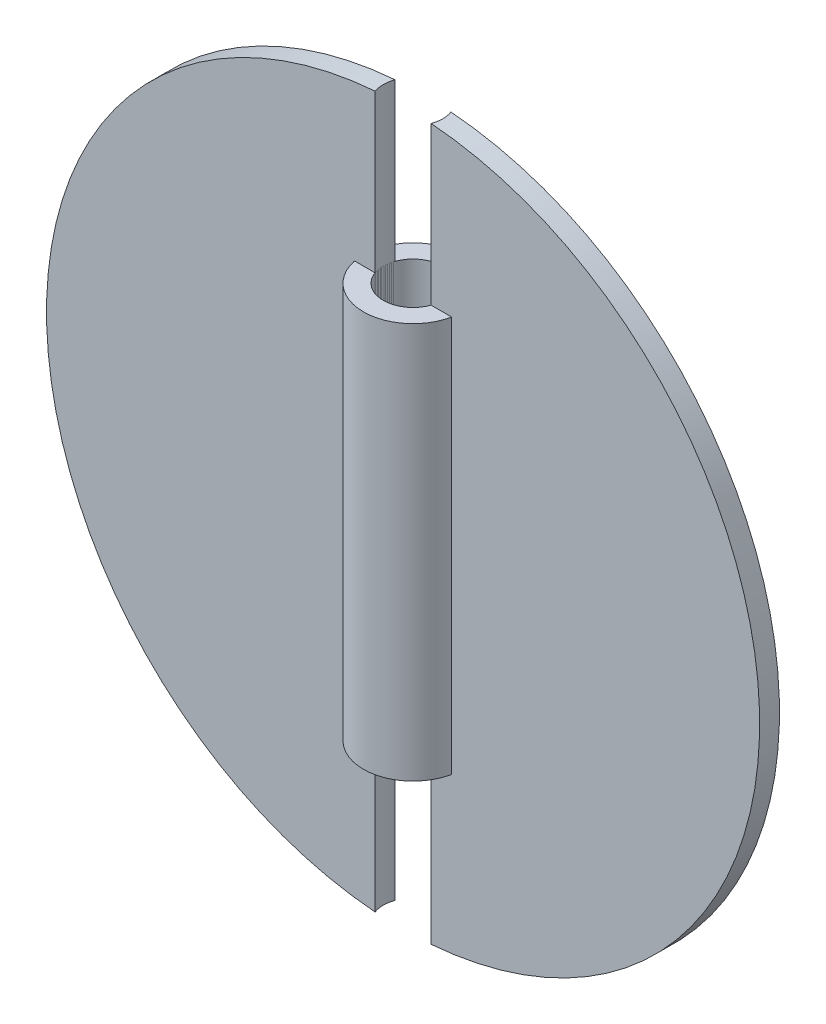
SolidWorks part; units mm, degrees
ref_plane "Front Plane" through (0, 0, 0) normal (0, 0, 1) x (1, 0, 0)
ref_plane "Top Plane" through (0, 0, 0) normal (0, 1, 0) x (1, 0, 0)
ref_plane "Right Plane" through (0, 0, 0) normal (1, 0, 0) x (0, 0, -1)
sketch "Sketch1" plane through (0, 0, 0) normal (0, 0, 1) x (1, 0, 0)
  circle A0 centre (0, 0) radius 38 construction
  circle A1 centre (0, 0) radius 36
  dimension "D1" = 76
  dimension "D2" = 2
extrude "Boss-Extrude1" add sketch "Sketch1" along normal blind 2
sketch "Sketch2" plane through (0, 0, 0) normal (0, 1, 0) x (1, 0, 0)
  line L0 (-2.3807, 0) -> (3.3426, 0) construction
  line L1 (36, 0) -> (-36, 0) construction
  line L2 (0, 0) -> (0, -2) construction
  line L3 (-36, -2) -> (36, -2) construction
  circle A0 centre (0, -1) radius 3
  circle A1 centre (0, -1) radius 5
  point P8 (0, -0.9556)
  point P9 (0, -1)
  dimension "D1" = 6
  dimension "D2" = 2
extrude "Boss-Extrude2" add sketch "Sketch2" against normal blind 20 and the other way blind 20.0001 separate body
sketch "Sketch3" plane through (0, 20.0001, 0) normal (0, 1, 0) x (1, 0, 0)
  circle A0 centre (0, -1) radius 3
extrude "Cut-Extrude1" cut sketch "Sketch3" against normal through all and the other way blind 20
